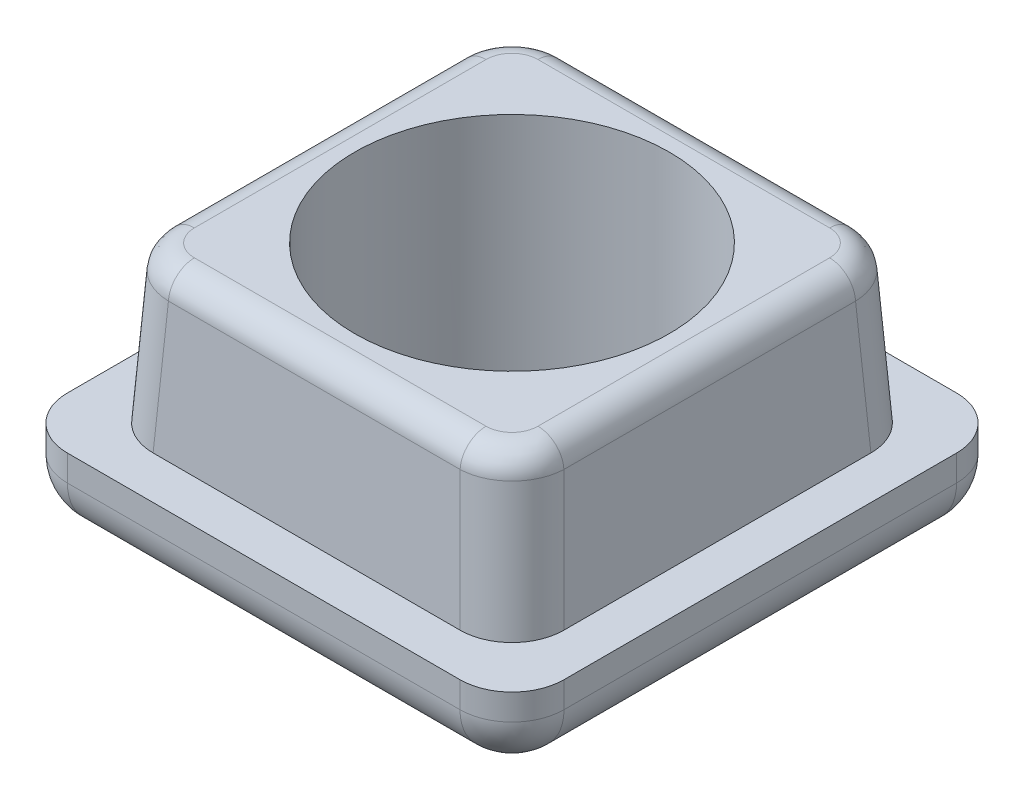
SolidWorks part; units mm, degrees
ref_plane "Front Plane" through (0, 0, 0) normal (0, 0, 1) x (1, 0, 0)
ref_plane "Top Plane" through (0, 0, 0) normal (0, 1, 0) x (1, 0, 0)
ref_plane "Right Plane" through (0, 0, 0) normal (1, 0, 0) x (0, 0, -1)
sketch "Sketch1" plane through (0, 0, 0) normal (0, 1, 0) x (1, 0, 0)
  line L1 (0, 0) -> (19.1, 0)
  line L2 (0, 0) -> (0, 19.1)
  line L3 (0, 19.1) -> (19.1, 19.1)
  line L4 (19.1, 0) -> (19.1, 19.1)
  dimension "D1" = 19.1
extrude "Boss-Extrude1" add sketch "Sketch1" along normal blind 3
sketch "Sketch2" plane through (0, 3, 0) normal (0, 1, 0) x (1, 0, 0)
  line L8 (1.65, 1.65) -> (17.45, 1.65)
  line L9 (17.45, 1.65) -> (17.45, 17.45)
  line L10 (1.65, 17.45) -> (1.65, 1.65)
  line L11 (17.45, 17.45) -> (1.65, 17.45)
  line L12 (1.65, 1.65) -> (17.45, 1.65)
  line L13 (17.45, 1.65) -> (17.45, 17.45)
  line L14 (1.65, 17.45) -> (1.65, 1.65)
  line L15 (17.45, 17.45) -> (1.65, 17.45)
  dimension "D1" = 1.65
ref_plane "Plane1" through (0, 9, 0) normal (0, 1, 0) x (1, 0, 0)
sketch "Sketch3" plane through (0, 9, 0) normal (0, 1, 0) x (1, 0, 0)
  line L8 (2, 2) -> (17.1, 2)
  line L9 (2, 17.1) -> (2, 2)
  line L10 (17.1, 17.1) -> (2, 17.1)
  line L11 (17.1, 2) -> (17.1, 17.1)
  line L12 (2, 2) -> (17.1, 2)
  line L13 (2, 17.1) -> (2, 2)
  line L14 (17.1, 17.1) -> (2, 17.1)
  line L15 (17.1, 2) -> (17.1, 17.1)
  dimension "D1" = 2
loft "Loft1" add profiles "Sketch2", "Sketch3" connector at (17.45, 3, -17.45) connector at (17.1, 9, -17.1)
sketch "Sketch4" plane through (0, 0, 0) normal (0, -1, 0) x (1, 0, 0)
  line L0 (0, 0) -> (19.1, 0) construction
  line L1 (0, -19.1) -> (0, 0) construction
  circle A0 centre (9.55, -9.55) radius 6.05
  point P4 (9.55, 0)
  point P7 (0, -9.55)
  dimension "D1" = 12.1
extrude "Cut-Extrude1" cut sketch "Sketch4" against normal through all
ref_plane "Plane2" through (9.55, 0, 0) normal (1, 0, 0) x (0, 0, -1)
ref_plane "Plane3" through (0, 0, -9.55) normal (0, 0, 1) x (1, 0, 0)
fillet "Fillet1" radius 2 8 edges at (19.1, 1.5, 0) (0, 1.5, 0) (19.1, 1.5, -19.1) (0, 1.5, -19.1)
fillet "Fillet2" radius 1 8 edges
fillet "Fillet3" radius 2 8 edges at (0.5858, 0, -0.5858) (0, 0, -9.55) (0.5858, 0, -18.5142) (9.55, 0, -19.1) (18.5142, 0, -18.5142) (19.1, 0, -9.55) (18.5142, 0, -0.5858) (9.55, 0, 0)
